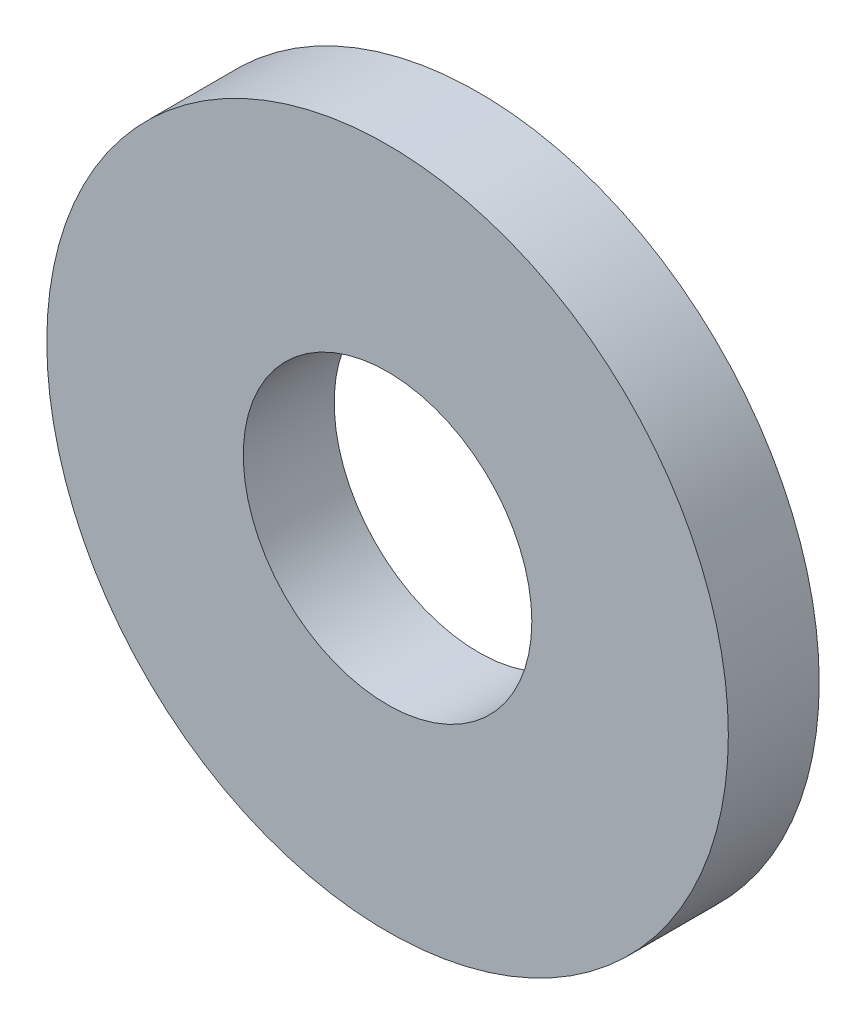
SolidWorks part; units mm, degrees
ref_plane "Front Plane" through (0, 0, 0) normal (0, 0, 1) x (1, 0, 0)
ref_plane "Top Plane" through (0, 0, 0) normal (0, 1, 0) x (1, 0, 0)
ref_plane "Right Plane" through (0, 0, 0) normal (1, 0, 0) x (0, 0, -1)
sketch "Sketch2" plane through (0, 0, 0) normal (0, 0, 1) x (1, 0, 0)
  circle A0 centre (0, 0) radius 6.35
  circle A1 centre (0, 0) radius 15
  dimension "D1" = 6.35
  dimension "D2" = 15
extrude "Extrude1" add sketch "Sketch2" along normal blind 4
ref_axis "Axis1" through (0, 0, -9.1242) along (0, 0, 1)
